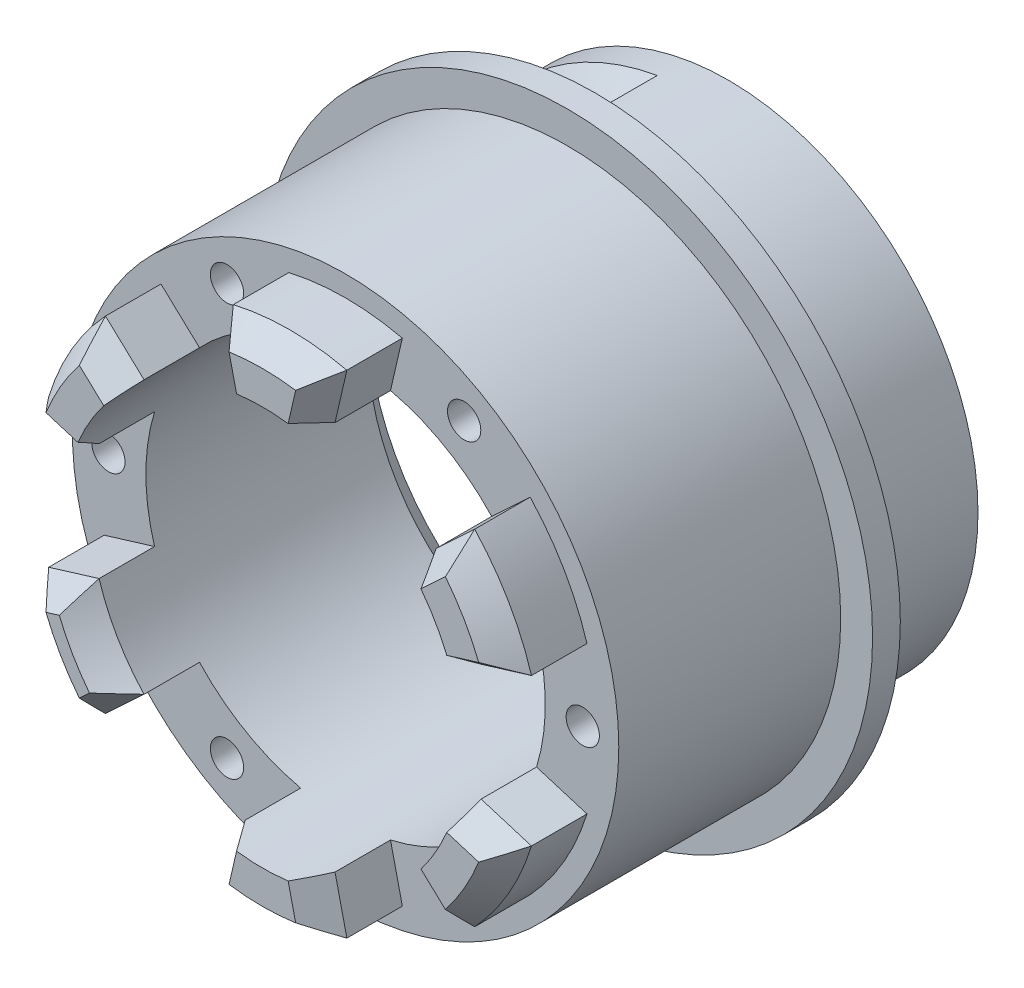
SolidWorks part; units mm, degrees
ref_plane "정면" through (0, 0, 0) normal (0, 0, 1) x (1, 0, 0)
ref_plane "윗면" through (0, 0, 0) normal (0, 1, 0) x (1, 0, 0)
ref_plane "우측면" through (0, 0, 0) normal (1, 0, 0) x (0, 0, -1)
sketch "스케치1" plane through (0, 0, 0) normal (0, 0, 1) x (1, 0, 0)
  circle A0 centre (0, 0) radius 9
  dimension "D1" = 18
extrude "보스-돌출1" add sketch "스케치1" along normal blind 2
sketch "스케치2" plane through (0, 0, 2) normal (0, 0, 1) x (1, 0, 0)
  circle A0 centre (0, 0) radius 9
  circle A1 centre (0, 0) radius 7.2
  circle A5 centre (0, 0) radius 9 construction
  dimension "D1" = 1.8
extrude "보스-돌출2" add sketch "스케치2" along normal blind 2.8
sketch "스케치4" plane through (0, 0, 4.8) normal (0, 0, 1) x (1, 0, 0)
  circle A0 centre (0, 0) radius 11
  circle A1 centre (0, 0) radius 7.2
  circle A2 centre (0, 0) radius 7.2 construction
  dimension "D1" = 22
extrude "보스-돌출3" add sketch "스케치4" along normal blind 1
sketch "스케치5" plane through (0, 0, 5.8) normal (0, 0, 1) x (1, 0, 0)
  circle A0 centre (0, 0) radius 7.2
  circle A1 centre (0, 0) radius 9.85
  circle A2 centre (0, 0) radius 7.2 construction
  dimension "D1" = 19.7
extrude "보스-돌출4" add sketch "스케치5" along normal blind 8
sketch "스케치6" plane through (0, 0, 13.8) normal (0, 0, 1) x (1, 0, 0)
  circle A0 centre (0, 0) radius 8.55 construction
  circle A6 centre (0, 0) radius 7.2 construction
  circle A8 centre (8.55, 0) radius 0.6
  circle A9 centre (4.275, -7.4045) radius 0.6
  circle A10 centre (-4.275, -7.4045) radius 0.6
  circle A11 centre (-8.55, 0) radius 0.6
  circle A12 centre (-4.275, 7.4045) radius 0.6
  circle A13 centre (4.275, 7.4045) radius 0.6
  point P19 (0, 0)
  point P20 (0, 0)
  dimension "D1" = 1.35
  dimension "D2" = 1.2
  dimension "D3" = 6
extrude "컷-돌출1" cut sketch "스케치6" against normal blind 8
sketch "스케치7" plane through (0, 0, 0) normal (0, 0, -1) x (-1, 0, 0)
  circle A0 centre (0, 0) radius 6 construction
  circle A5 centre (0, 0) radius 3
  circle A6 centre (-6, 0) radius 1.1
  circle A7 centre (6, 0) radius 1.1
  circle A9 centre (0, 6) radius 1.1
  circle A11 centre (0, -6) radius 1.1
  dimension "D1" = 12
  dimension "D2" = 2.2
  dimension "D4" = 6
extrude "컷-돌출2" cut sketch "스케치7" against normal through all
sketch "스케치10" plane through (0, 0, 13.8) normal (0, 0, 1) x (1, 0, 0)
  line L24 (2.0471, 8.8668) -> (1.6196, 7.0155)
  line L25 (-2.0471, 8.8668) -> (-1.6196, 7.0155)
  line L26 (6.6553, 6.2062) -> (5.2657, 4.9104)
  line L27 (8.7024, 2.6606) -> (6.8854, 2.1051)
  line L28 (8.7024, -2.6606) -> (6.8854, -2.1051)
  line L29 (6.6553, -6.2062) -> (5.2657, -4.9104)
  line L30 (2.0471, -8.8668) -> (1.6196, -7.0155)
  line L31 (-2.0471, -8.8668) -> (-1.6196, -7.0155)
  line L32 (-6.6553, -6.2062) -> (-5.2657, -4.9104)
  line L33 (-8.7024, -2.6606) -> (-6.8854, -2.1051)
  line L34 (-8.7024, 2.6606) -> (-6.8854, 2.1051)
  line L35 (-6.6553, 6.2062) -> (-5.2657, 4.9104)
  arc A0 (-6.6553, 6.2062) -> (-8.7024, 2.6606) centre (0, 0) ccw
  arc A1 (-6.8854, -2.1051) -> (-5.2657, -4.9104) centre (0, 0) ccw
  arc A2 (2.0471, 8.8668) -> (-2.0471, 8.8668) centre (0, 0) ccw
  arc A3 (8.7024, 2.6606) -> (6.6553, 6.2062) centre (0, 0) ccw
  arc A4 (6.6553, -6.2062) -> (8.7024, -2.6606) centre (0, 0) ccw
  arc A5 (-2.0471, -8.8668) -> (2.0471, -8.8668) centre (0, 0) ccw
  arc A6 (-8.7024, -2.6606) -> (-6.6553, -6.2062) centre (0, 0) ccw
  arc A7 (-1.6196, -7.0155) -> (1.6196, -7.0155) centre (0, 0) ccw
  arc A8 (5.2657, -4.9104) -> (6.8854, -2.1051) centre (0, 0) ccw
  arc A9 (6.8854, 2.1051) -> (5.2657, 4.9104) centre (0, 0) ccw
  arc A10 (1.6196, 7.0155) -> (-1.6196, 7.0155) centre (0, 0) ccw
  arc A11 (-5.2657, 4.9104) -> (-6.8854, 2.1051) centre (0, 0) ccw
  circle A12 centre (0, 0) radius 7.2 construction
  circle A17 centre (0, 0) radius 7.2 construction
  point P9 (0, 0)
  point P10 (0, 0)
  point P21 (0, 0)
  point P30 (0, 0)
  point P48 (0, 0)
  point P61 (0, 0)
  dimension "D1" = 1.9
  dimension "D4" = 6
extrude "보스-돌출5" add sketch "스케치10" along normal blind 3
chamfer "모따기1" distance 1 angle 35 19 edges at (-7.8808, -4.55, 16.8) (0, -9.1, 16.8) (7.8808, -4.55, 16.8) (7.8808, 4.55, 16.8) (0, 9.1, 16.8) (-7.8808, 4.55, 16.8) (-7.7939, -2.3828, 16.8) (-6.2354, -3.6, 16.8) (-5.9605, -5.5583, 16.8) (1.8334, -7.9411, 16.8) (-1.8334, -7.9411, 16.8) (5.9605, -5.5583, 16.8) (7.7939, -2.3828, 16.8) (7.7939, 2.3828, 16.8) (5.9605, 5.5583, 16.8) (1.8334, 7.9411, 16.8) (-1.8334, 7.9411, 16.8) (-7.7939, 2.3828, 16.8) (-5.9605, 5.5583, 16.8) first distance on face at (-7.7798, -4.4917, 15.3) first distance on face at (0, -8.9834, 15.3) first distance on face at (7.7798, -4.4917, 15.3) first distance on face at (7.7798, 4.4917, 15.3) first distance on face at (0, 8.9834, 15.3) first distance on face at (-7.7798, 4.4917, 15.3) first distance on face at (-7.7939, -2.3828, 15.3) first distance on face at (7.2, 0, 2) first distance on face at (-5.9605, -5.5583, 15.3) first distance on face at (1.8334, -7.9411, 15.3) first distance on face at (-1.8334, -7.9411, 15.3) first distance on face at (5.9605, -5.5583, 15.3) first distance on face at (7.7939, -2.3828, 15.3) first distance on face at (7.7939, 2.3828, 15.3) first distance on face at (5.9605, 5.5583, 15.3) first distance on face at (1.8334, 7.9411, 15.3) first distance on face at (-1.8334, 7.9411, 15.3) first distance on face at (-7.7939, 2.3828, 15.3) first distance on face at (-5.9605, 5.5583, 15.3)
sketch "스케치11" plane through (0, 0, 0) normal (0, 0, -1) x (-1, 0, 0)
  line L0 (0, 0) -> (1.7365, 9.8481)
  line L1 (0, 0) -> (1.7365, -9.8481)
  line L2 (0, 0) -> (10, 0) construction
  circle A0 centre (0, 0) radius 10
  circle M6 centre (6, 0) radius 1.1
  circle M9 centre (0, 0) radius 3
  circle M10 centre (0, 0) radius 9
  dimension "D1" = 80
  dimension "D2" = 80
extrude "컷-돌출3" cut sketch "스케치11" against normal blind 2.8 from offset 2 contours L2 A0 L0 M9 M6 | L2 L1 M9 M10 M6 region at (-4.5289, 3.9797, 0) region at (-4.5289, -3.9797, 0) offset against normal yes
chamfer "모따기2" distance 1 angle 45 2 edges at (-7.2, 0, 4.8) (-9, 0, 2)
